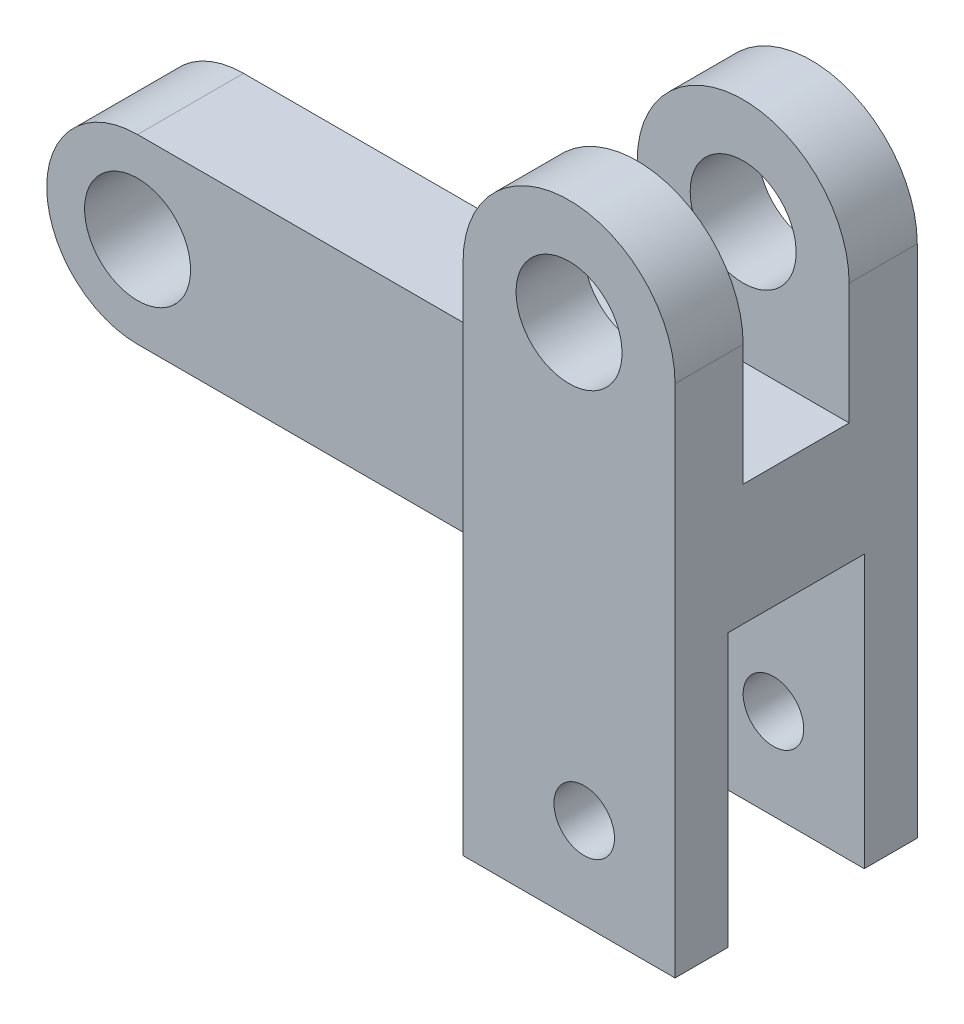
SolidWorks part; units mm, degrees
ref_plane "前视基准面" through (0, 0, 0) normal (0, 0, 1) x (1, 0, 0)
ref_plane "上视基准面" through (0, 0, 0) normal (0, 1, 0) x (1, 0, 0)
ref_plane "右视基准面" through (0, 0, 0) normal (1, 0, 0) x (0, 0, -1)
other "Configuration Table"
sketch "草图1" plane through (0, 0, 0) normal (0, 1, 0) x (1, 0, 0)
  line L1 (0, 3.5) -> (7, 3.5)
  line L2 (0, -3.5) -> (7, -3.5)
  line L3 (0, 3.5) -> (7, 3.5) construction
  line L4 (7, 3.5) -> (7, -3.5)
  line L5 (0, 3.5) -> (0, -3.5)
  dimension "D1" = 7
  dimension "D4" = 90
  dimension "D5" = 7
extrude "凸台-拉伸1" add sketch "草图1" along normal blind 2.4
sketch "草图10" plane through (0, 0, -3.5) normal (0, 0, -1) x (-1, 0, 0)
  line L3 (-7, 2.4) -> (0, 2.4) construction
  line L6 (-7, 2.4) -> (0, 2.4)
  line L7 (0, 2.4) -> (0, 10)
  line L9 (-7, 10) -> (-7, 2.4)
  line L10 (0, 2.4) -> (0, 0) construction
  arc A1 (0, 10) -> (-7, 10) centre (-3.5, 10) ccw
  line M3 (0, 2.4) -> (-7, 2.4)
  dimension "D8" = 3.5
  dimension "D9" = 10
extrude "凸台-拉伸6" add sketch "草图10" against normal blind 1.75 contours L7 A1 L9 M3 region at (3.5, 7.6039, -3.5)
extrude "凸台-拉伸8" add sketch "草图10<2>" along normal blind 1.75 from offset 7 contours L7 A1 L9 M3 region at (3.5, 7.6039, -3.5) offset against normal yes
sketch "草图10<2>" plane through (0, 0, -3.5) normal (0, 0, -1) x (-1, 0, 0) same geometry as "草图10"
sketch "草图11" plane through (0, 0, -3.5) normal (0, 0, -1) x (-1, 0, 0)
  circle A2 centre (-3.5, 10) radius 1.75
  dimension "D3" = 3.5
extrude "切除-拉伸1" cut sketch "草图11" against normal through all
sketch "草图17" plane through (0, 0, 0) normal (0, -1, 0) x (1, 0, 0)
  line L6 (0, 3.5) -> (0, -3.5)
  line L7 (0, -3.5) -> (7, -3.5)
  line L8 (7, -3.5) -> (7, 3.5)
  line L9 (7, 3.5) -> (0, 3.5)
  line L12 (0, 3.5) -> (0, -3.5)
  line L13 (0, -3.5) -> (7, -3.5)
  line L14 (7, -3.5) -> (7, 3.5)
  line L15 (7, 3.5) -> (0, 3.5)
  dimension "D1" = 0
extrude "凸台-拉伸10" add sketch "草图17" along normal blind 7
sketch "草图15" plane through (0, 0, 0) normal (0, 0, 1) x (1, 0, 0)
  line L2 (7, 6) -> (7, 0)
  line L10 (7, 10) -> (7, -7) construction
  line L14 (-13, 6) -> (7, 6)
  line L15 (7, 10) -> (7, -7) construction
  line L17 (7, 2.4) -> (7.3779, 2.4)
  line L18 (0, 2.4) -> (7, 2.4) construction
  line L19 (-13, 0) -> (7, 0)
  line L20 (7, -7) -> (0, -7) construction
  arc A0 (-13, 0) -> (-13, 6) centre (-13, 3) cw
  circle A1 centre (-13, 3) radius 1.75
  dimension "D3" = 3.5
  dimension "D1" = 3
  dimension "D2" = 7
  dimension "D4" = 20
extrude "凸台-拉伸9" add sketch "草图15" along normal mid plane 3.5 contours A0 L19 L2 L14 A1 region at (-3.5072, 3, 0)
sketch "草图12" plane through (0, 4, 3.5) normal (0, 0, -1) x (1, 0, 0)
  line L0 (0, 11) -> (7, 11) construction
  line L2 (7, -6) -> (7, 11) construction
  circle A0 centre (4, 8) radius 1
  dimension "D2" = 2
  dimension "D1" = 3
  dimension "D3" = 3
extrude "切除-拉伸2" cut sketch "草图12" along normal through all
sketch "草图18" plane through (7.4, -7, 0) normal (0, 1, 0) x (1, 0, 0)
  line L0 (-0.4, 1.75) -> (-0.4, 3.5) construction
  line L11 (-7.4, -2.25) -> (-0.4, -2.25)
  line L12 (-7.4, -2.25) -> (-7.4, 2.25)
  line L13 (-7.4, 2.25) -> (-0.4, 2.25)
  line L14 (-0.4, -2.25) -> (-0.4, 2.25)
  point P4 (-7.4, 0)
  dimension "D1" = 4.5
  dimension "D2" = 7
extrude "切除-拉伸4" cut sketch "草图18" along normal blind 9
sketch "草图19" plane through (0, 0, 3.5) normal (0, 0, 1) x (1, 0, 0)
  line L4 (0, 10) -> (0, -7)
  line L5 (0, -7) -> (7, -7)
  line L6 (7, -7) -> (7, 10)
  line L8 (0, 10) -> (0, -7)
  line L9 (0, -7) -> (7, -7)
  line L10 (7, -7) -> (7, 10)
  circle A0 centre (4, -4) radius 1 construction
  circle A1 centre (4, -4) radius 1
  circle A2 centre (3.5, 10) radius 1.75 construction
  arc A3 (7, 10) -> (0, 10) centre (3.5, 10) ccw
  arc A4 (7, 10) -> (0, 10) centre (3.5, 10) ccw
  circle A5 centre (3.5, 10) radius 1.75
  dimension "D1" = 0
extrude "凸台-拉伸11" add sketch "草图19" along normal blind 0.5
sketch "草图20" plane through (0, 0, -3.5) normal (0, 0, -1) x (-1, 0, 0)
  line L4 (-7, 10) -> (-7, -7)
  line L5 (-7, -7) -> (0, -7)
  line L6 (0, -7) -> (0, 10)
  line L8 (-7, 10) -> (-7, -7)
  line L9 (-7, -7) -> (0, -7)
  line L10 (0, -7) -> (0, 10)
  circle A0 centre (-4, -4) radius 1 construction
  circle A1 centre (-4, -4) radius 1
  circle A2 centre (-3.5, 10) radius 1.75 construction
  arc A3 (0, 10) -> (-7, 10) centre (-3.5, 10) ccw
  arc A4 (0, 10) -> (-7, 10) centre (-3.5, 10) ccw
  circle A5 centre (-3.5, 10) radius 1.75
  dimension "D1" = 0
extrude "凸台-拉伸12" add sketch "草图20" along normal blind 0.5
